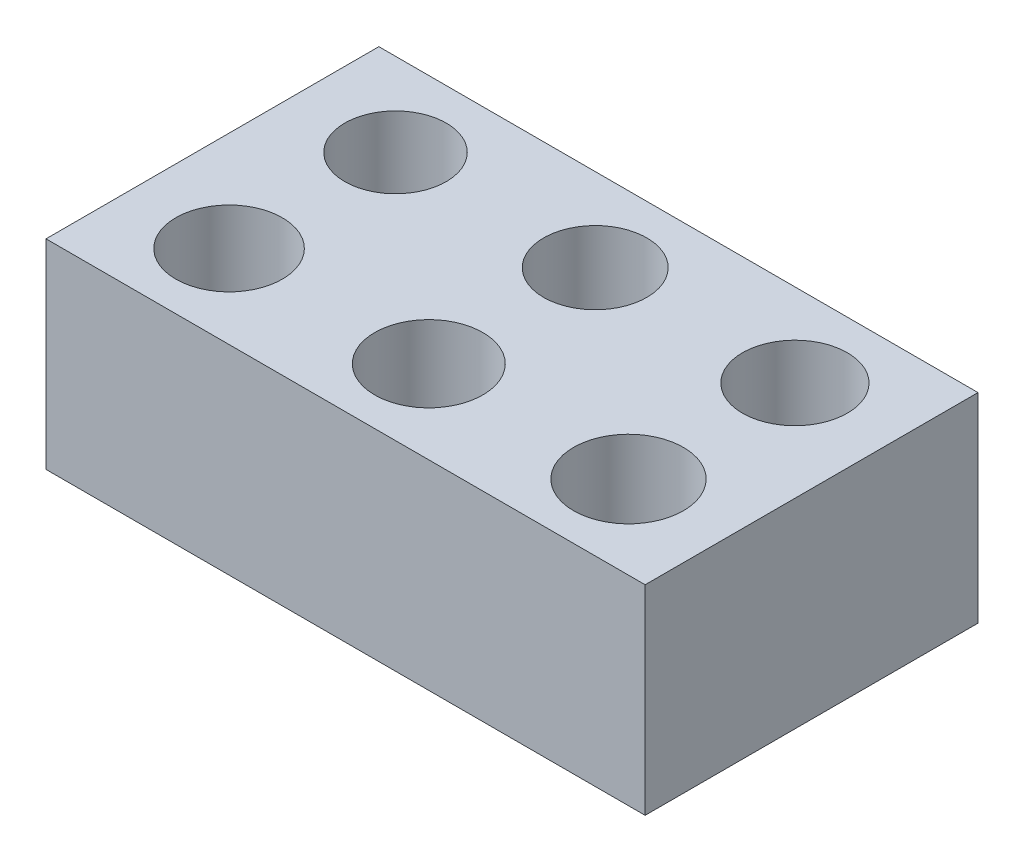
SolidWorks part; units mm, degrees
ref_plane "Front Plane" through (0, 0, 0) normal (0, 0, 1) x (1, 0, 0)
ref_plane "Top Plane" through (0, 0, 0) normal (0, 1, 0) x (1, 0, 0)
ref_plane "Right Plane" through (0, 0, 0) normal (1, 0, 0) x (0, 0, -1)
sketch "Sketch1" plane through (0, 0, 0) normal (0, 1, 0) x (1, 0, 0)
  line L1 (-9, -5) -> (9, -5)
  line L2 (-9, -5) -> (-9, 5)
  line L3 (-9, 5) -> (9, 5)
  line L4 (9, -5) -> (9, 5)
  line L5 (-9, -5) -> (9, 5) construction
  line L6 (-9, 5) -> (9, -5) construction
  circle A0 centre (-6, 2.5) radius 1.525
  circle A1 centre (0, 2.5) radius 1.55
  circle A2 centre (6, 2.5) radius 1.575
  circle A3 centre (-6, -2.5) radius 1.6
  circle A4 centre (0, -2.5) radius 1.625
  circle A5 centre (6, -2.5) radius 1.65
  point P0 (0, 0)
  point P18 (-10.0767, -2.3074)
  point P19 (-9.5, -2.3074)
  point P20 (-0.92, 2)
  point P21 (-0.92, -2)
  point P22 (8.372, -2)
  point P23 (-3.5481, -2)
  point P24 (0, 0)
  point P25 (-2.434, 2)
  point P26 (-3.5481, 2)
  point P27 (1.7993, -2)
  point P28 (13.2148, 7.3416)
  point P29 (6.4893, 2.7635)
  point P30 (6.0195, -2)
  point P31 (0, -2.4046)
  point P32 (0, 2.7635)
  point P33 (-5.8305, 2)
  point P34 (-5.8305, -2)
  point P35 (0, 0)
  point P36 (0, 0)
  point P37 (0, 2.5)
  dimension "D1" = 3.05
  dimension "D2" = 3.1
  dimension "D3" = 3.15
  dimension "D4" = 3.2
  dimension "D5" = 3.25
  dimension "D6" = 3.3
  dimension "D7" = 10
  dimension "D8" = 18
  dimension "D9" = 3
  dimension "D10" = 3
  dimension "D11" = 3
  dimension "2.5" = 2.5
  dimension "D12" = 2.5
  dimension "D13" = 2.5
  dimension "D14" = 2.5
  dimension "D15" = 2.5
  dimension "D16" = 2.5
extrude "Boss-Extrude1" add sketch "Sketch1" against normal blind 6 contours A3 | A0 | L1 L4 L3 L2 A5 A4 A3 A2 A1 A0 | A1 | A4 | A5 | A2 region at (-0.0452, 0, -0.0424) region at (-6, 0, -2.5) region at (0, 0, -2.5) region at (6, 0, -2.5) region at (-6, 0, 2.5) region at (0, 0, 2.5) region at (6, 0, 2.5)
extrude "Cut-Extrude1" cut sketch "Sketch1<3>" against normal blind 4 contours A0 | A3 | A1 | A4 | A5 | A2 region at (-6, 0, -2.5) region at (0, 0, -2.5) region at (6, 0, -2.5) region at (-6, 0, 2.5) region at (0, 0, 2.5) region at (6, 0, 2.5)
sketch "Sketch1<3>" plane through (0, 0, 0) normal (0, 1, 0) x (1, 0, 0) same geometry as "Sketch1"
